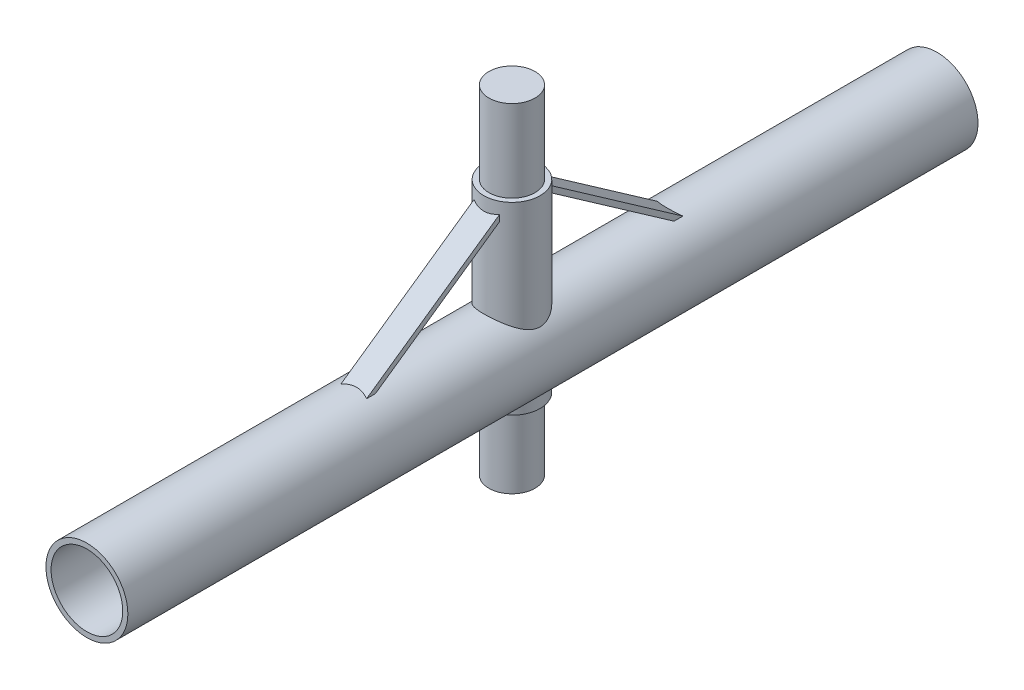
SolidWorks part; units mm, degrees
ref_plane "Front Plane" through (0, 0, 0) normal (0, 0, 1) x (1, 0, 0)
ref_plane "Top Plane" through (0, 0, 0) normal (0, 1, 0) x (1, 0, 0)
ref_plane "Right Plane" through (0, 0, 0) normal (1, 0, 0) x (0, 0, -1)
sketch "Sketch1" plane through (0, 0, 0) normal (0, 0, 1) x (1, 0, 0)
  circle A0 centre (0, 0) radius 60
  dimension "D1" = 120
extrude "Extrude-Thin1" add sketch "Sketch1" along normal mid plane 1245 thin contours A0 thin type one direction reverse wall 7.5
sketch "Sketch2" plane through (0, 0, 0) normal (0, 1, 0) x (1, 0, 0)
  circle A0 centre (0, 0) radius 33.75
  dimension "D1" = 67.5
extrude "Extrude-Thin2" add sketch "Sketch2" along normal blind 210 and the other way blind 60 thin
sketch "Sketch3" plane through (0, 210, 0) normal (0, 1, 0) x (1, 0, 0)
  circle A0 centre (0, 0) radius 33.75 construction
  circle A1 centre (0, 0) radius 33.75
extrude "Boss-Extrude1" add sketch "Sketch3" along normal blind 120 and the other way offset from surface (375 mm away) 105 other way up to face at (0, -60, 0)
sketch "Sketch4" plane through (0, 0, 0) normal (1, 0, 0) x (0, 0, -1)
  line L0 (0, 210) -> (-300, 0)
  dimension "D1" = 300
  dimension "D2" = 210
extrude "Extrude-Thin3" add sketch "Sketch4" along normal mid plane 37.5 separate body thin
mirror "Mirror2" about plane through (0, 0, 0) normal (0, 0, 1) of "Extrude-Thin3"
sketch "Sketch5" plane through (0, 0, -622.5) normal (0, 0, -1) x (-1, 0, 0)
  circle A0 centre (0, 0) radius 52.5 construction
  circle A1 centre (0, 0) radius 52.5
extrude "Cut-Extrude1" cut sketch "Sketch5" against normal through all
